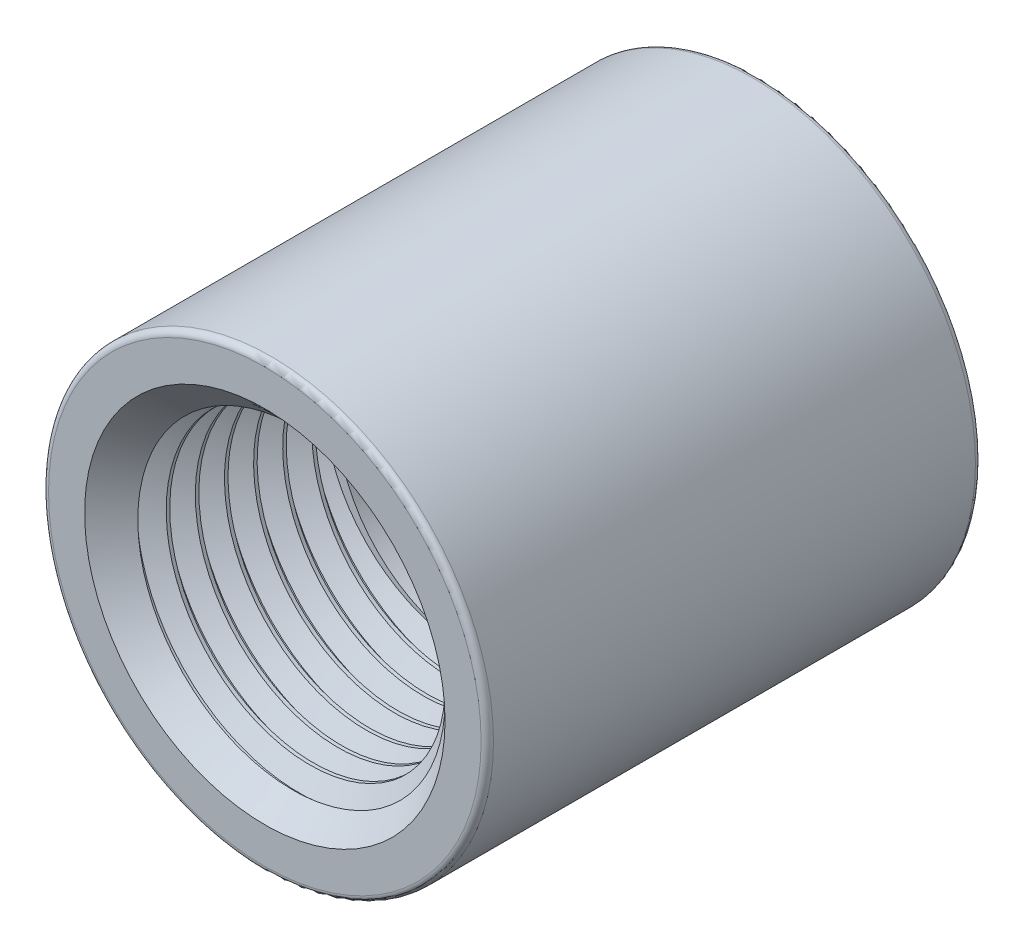
SolidWorks part; units mm, degrees
ref_plane "Front Plane" through (0, 0, 0) normal (0, 0, 1) x (1, 0, 0)
ref_plane "Top Plane" through (0, 0, 0) normal (0, 1, 0) x (1, 0, 0)
ref_plane "Right Plane" through (0, 0, 0) normal (1, 0, 0) x (0, 0, -1)
sketch "Sketch0" plane through (0, 0, 0) normal (1, 0, 0) x (0, 0, -1)
  line L0 (15.875, 0) -> (-15.875, 0) construction
  line L1 (-15.875, 14.2875) -> (-15.875, -14.2875) construction
  line L3 (0, 0) -> (-15.875, 0) construction
  line L11 (0, 8.9297) -> (0, -8.9297) construction
  line L12 (-15.875, 10.668) -> (-15.875, -10.668)
  point P25 (-2.319, 0)
sketch "Sketch1" plane through (0, 0, 0) normal (0, 0, 1) x (1, 0, 0)
  circle A0 centre (0, 0) radius 14.2875
extrude "Extrude1" add sketch "Sketch1" along normal up to vertex (15.875 mm away) and the other way up to vertex (15.875 mm away) up to point (0, 0, 15.875) other way up to point (0, 0, -15.875)
sketch "Sketch2" plane through (0, 0, 15.875) normal (0, 0, 1) x (1, 0, 0)
  circle A0 centre (0, 0) radius 8.9297
extrude "Extrude2" cut sketch "Sketch2" against normal blind 19.8501
sketch "Sketch2.1" plane through (0, 0, 0) normal (1, 0, 0) x (0, 0, -1)
  line L0 (0, 0) -> (3.9751, 0) construction
  line L1 (3.9751, 8.9297) -> (3.9751, -8.9297) construction
  line L2 (3.9751, 0) -> (9.3406, 0)
  line L3 (3.9751, 8.9297) -> (23.0251, 8.9297)
  line L4 (3.9751, 8.9297) -> (3.9751, 0)
  line L5 (23.0251, 8.9297) -> (23.0251, 0)
  line L6 (23.0251, 0) -> (9.3406, 0)
  dimension "D1" = 19.05
revolve "Cut-Revolve1" cut sketch "Sketch2.1" angle 360 about L0
sketch "Sketch3" plane through (0, 0, 15.875) normal (0, 0, 1) x (1, 0, 0)
  circle A0 centre (0, 0) radius 10.668
extrude "Extrude3" cut sketch "Sketch3" against normal up to vertex (13.556 mm away) draft 1.783 up to point (0, 0, 2.319)
sketch "Sketch4" plane through (0, 0, 15.875) normal (0, 0, 1) x (1, 0, 0)
  circle A1 centre (0, 0) radius 10.668
  circle A2 centre (0, 0) radius 10.668
  dimension "D1" = 0
curve "Helix/Spiral1" parameters "L"=15.3703, "Pitch"=1.8143, "A"=1.783
sketch "Sketch5" plane through (0, 0, 0) normal (1, 0, 0) x (0, 0, -1)
  line L0 (-16.7821, 10.8644) -> (-14.9679, 10.8644)
  line L1 (-14.9679, 10.8644) -> (-15.7616, 9.4896)
  line L2 (-15.7616, 9.4896) -> (-15.9884, 9.4896)
  line L3 (-15.9884, 9.4896) -> (-16.7821, 10.8644)
  line L4 (-15.875, 10.8644) -> (-15.875, 9.4896) construction
  line L5 (-16.6687, 10.668) -> (-15.0813, 10.668) construction
  point P8 (-15.875, 10.668)
  dimension "D1" = 1.8143
  dimension "D2" = 0.2268
  dimension "D3" = 1.5875
  dimension "D4" = 60
sweep "Sweep1" add profiles "Sketch5" path "Helix/Spiral1"
sketch "Sketch6" plane through (0, 0, 15.875) normal (0, 0, 1) x (1, 0, 0)
  circle A0 centre (0, 0) radius 11.5751
  circle A1 centre (0, 0) radius 10.668
  circle A2 centre (0, 0) radius 10.668 construction
  dimension "D2" = 0.9071
extrude "Extrude4" cut sketch "Sketch6" against normal through all draft 45 and the other way through all draft 45
fillet "Fillet1" radius 0.3969 2 edges at (14.2875, 0, -15.875) (14.2875, 0, 15.875)
equation "\"A@Helix/Spiral1\" = \"A@Extrude3\""
equation "\"L@Helix/Spiral1\" = \"Pitch@Helix/Spiral1\" + \"L2@Sketch0\""
equation "\"D1@Sketch5\" = \"Pitch@Helix/Spiral1\""
equation "\"D2@Sketch5\" = \"D1@Sketch5\" * 1 / 8"
equation "\"D3@Sketch5\" = \"D1@Sketch5\" * 7 / 8"
equation "\"D2@Sketch6\" = \"Pitch@Helix/Spiral1\" * 1 / 2"
